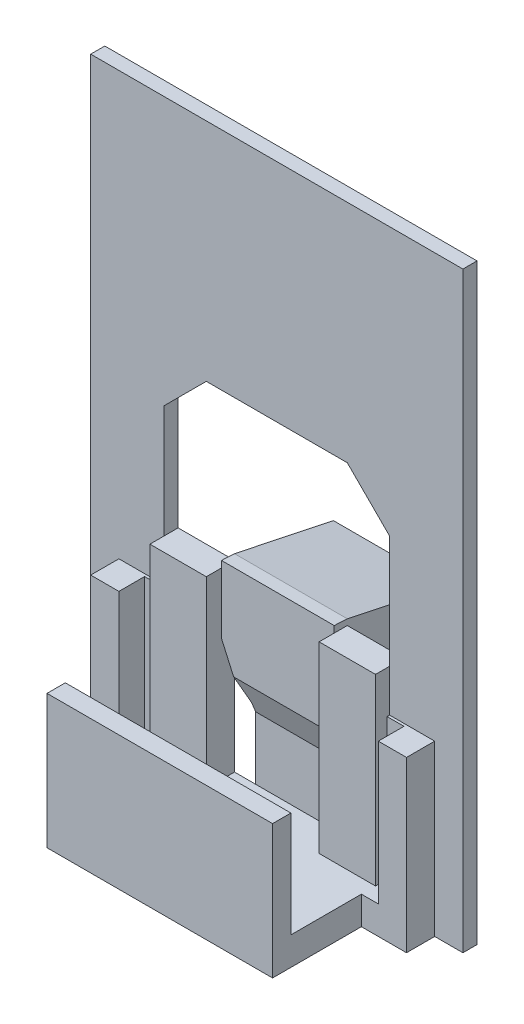
SolidWorks part; units mm, degrees
ref_plane "前视基准面" through (0, 0, 0) normal (0, 0, 1) x (1, 0, 0)
ref_plane "上视基准面" through (0, 0, 0) normal (0, 1, 0) x (1, 0, 0)
ref_plane "右视基准面" through (0, 0, 0) normal (1, 0, 0) x (0, 0, -1)
sketch "草图1" plane through (0, 0, 0) normal (0, 1, 0) x (1, 0, 0)
  line L1 (8, -4.75) -> (-8, -4.75)
  line L2 (8, -4.75) -> (8, 4.75)
  line L3 (8, 4.75) -> (-8, 4.75)
  line L4 (-8, -4.75) -> (-8, 4.75)
  line L5 (8, -4.75) -> (-8, 4.75) construction
  line L6 (8, 4.75) -> (-8, -4.75) construction
  line L7 (8, 4.75) -> (-8, 4.75)
  line L8 (8, 4.75) -> (8, 2.75)
  line L9 (8, 2.75) -> (-8, 2.75)
  line L10 (-8, 4.75) -> (-8, 2.75)
  line L11 (8, -4.75) -> (-8, -4.75)
  line L12 (8, -4.75) -> (8, -3.25)
  line L13 (8, -3.25) -> (-8, -3.25)
  line L14 (-8, -4.75) -> (-8, -3.25)
  point P0 (0, 0)
  dimension "D1" = 6
  dimension "D2" = 9.5
  dimension "D3" = 2
  dimension "D4" = 16
extrude "凸台-拉伸1" add sketch "草图1" along normal blind 2 contours L13 L2 L9 L4 region at (0, 0, 0.25)
extrude "凸台-拉伸2" add sketch "草图1<3>" along normal blind 15 contours L9 L2 L3 L4 | L2 L13 L4 L1 region at (0, 0, 4) region at (0, 0, -3.75)
sketch "草图1<3>" plane through (0, 0, 0) normal (0, 1, 0) x (1, 0, 0) same geometry as "草图1"
sketch "草图2" plane through (0, 0, -4.75) normal (0, 0, -1) x (-1, 0, 0)
  line L0 (0, 12.199) -> (0, -4.867) construction
  line L1 (-8, 15) -> (8, 15) construction
  line L2 (4, 28) -> (-4, 28)
  line L3 (4, 28) -> (4, 2)
  line L4 (4, 2) -> (-4, 2)
  line L5 (-4, 28) -> (-4, 2)
  line L6 (4, 28) -> (-4, 2) construction
  line L7 (4, 2) -> (-4, 28) construction
  line L8 (-8, 2) -> (8, 2) construction
  point P3 (0, 15)
  dimension "D1" = 8
  dimension "D2" = 0
extrude "切除-拉伸1" cut sketch "草图2" against normal up to surface (2 mm away) up to face at (0, 8.5, -2.75)
sketch "草图3" plane through (0, 0, 0) normal (1, 0, 0) x (0, 0, -1)
  line L0 (4.75, 0) -> (8.8316, 0)
  line L3 (4.75, 15.4148) -> (4.75, 0)
  line L4 (4.75, 15.4148) -> (11.7685, 13.9357)
  line L5 (11.7685, 13.9357) -> (8.8316, 0)
  dimension "D1" = 90
extrude "凸台-拉伸3" add sketch "草图3" along normal mid plane 5
sketch "草图4" plane through (8, 0, 0) normal (1, 0, 0) x (0, 0, -1)
  line L0 (2.75, 15) -> (2.75, 2) construction
  line L1 (4.75, 15) -> (2.75, 15)
  line L2 (4.75, 15) -> (4.75, 11.7656)
  line L3 (4.75, 11.7656) -> (2.75, 11.7656)
  line L4 (2.75, 15) -> (2.75, 11.7656)
sketch "草图5" plane through (2.5, 0, 0) normal (1, 0, 0) x (0, 0, -1)
  line L0 (4.75, 6.4511) -> (3.8228, 8.745)
  line L1 (4.75, 15) -> (4.75, 0) construction
  line L2 (3.8228, 8.745) -> (3.8228, 15.4638)
  line L3 (2.7617, 15.5198) -> (10.7506, 15.0981) construction
  line L4 (3.8228, 15.4638) -> (4.75, 15.4148)
  line L5 (4.75, 15.4148) -> (4.75, 6.4511)
extrude "凸台-拉伸4" add sketch "草图5" against normal up to surface (5 mm away) up to face at (-2.5, 6.2701, -6.97)
sketch "草图6" plane through (-2.5, 0, 0) normal (-1, 0, 0) x (0, 0, 1)
  line L0 (-4.75, 6.4511) -> (-10.0949, 5.9946)
  line L7 (-4.75, 2) -> (-4.75, 6.4511)
  line L8 (-4.75, 6.4511) -> (-3.8228, 8.745)
  line L9 (-3.8228, 8.745) -> (-3.8228, 15.4638)
  line L10 (-3.8228, 15.4638) -> (-4.75, 15.4148)
  line L11 (-3.8228, 15.4638) -> (-4.75, 15.4148)
  line L12 (-8.8316, 0) -> (-4.75, 0)
  line L13 (-4.75, 0) -> (-4.75, 2)
  line L15 (-4.75, 6.4511) -> (-3.8228, 8.745)
  line L16 (-3.8228, 8.745) -> (-3.8228, 15.4638)
  line L22 (-4.75, 15.4148) -> (-11.7685, 13.9357)
  line L23 (-4.75, 15.4148) -> (-11.7685, 13.9357)
  line L24 (-11.7685, 13.9357) -> (-8.8316, 0)
  line L25 (-11.7685, 13.9357) -> (-10.0949, 5.9946)
  dimension "D1" = 0
extrude "凸台-拉伸5" add sketch "草图6" along normal up to surface (1.5 mm away) up to face at (-4, 8.5, -3.75)
sketch "草图9" plane through (0, 0, 0) normal (0, -1, 0) x (1, 0, 0)
  line L0 (8, -4.75) -> (11.2, -4.75)
  line L1 (11.2, -4.75) -> (11.2, -1.75)
  line L2 (11.2, -1.75) -> (9.2, -1.75)
  line L4 (8, -3.5704) -> (8, -4.75)
  line L5 (9.2, -1.75) -> (9.2, -3.5704)
  line L6 (9.2, -3.5704) -> (8, -3.5704)
  line L7 (9.2, -1.75) -> (8, -1.75)
  line L8 (8, 4.75) -> (8, -4.75) construction
  line L9 (8, -1.75) -> (8, -3.5704)
  line L10 (0, 0) -> (0, -12.5877) construction
  line L11 (-8, -1.75) -> (-8, -3.5704)
  line L12 (-9.2, -1.75) -> (-8, -1.75)
  line L13 (-9.2, -3.5704) -> (-8, -3.5704)
  line L14 (-9.2, -1.75) -> (-9.2, -3.5704)
  line L15 (-8, -3.5704) -> (-8, -4.75)
  line L16 (-11.2, -1.75) -> (-9.2, -1.75)
  line L17 (-11.2, -4.75) -> (-11.2, -1.75)
  line L18 (-8, -4.75) -> (-11.2, -4.75)
  line M7 (8, -4.75) -> (8, 4.75)
  line M9 (-8, 4.75) -> (-8, -4.75)
  dimension "D1" = 3
  dimension "D2" = 1.2
  dimension "D3" = 2
extrude "凸台-拉伸6" add sketch "草图9" against normal up to surface (2 mm away) contours L5 L7 L6 M7 | L12 L14 L13 M9 region at (8.6, 0, -2.6602) region at (-8.6, 0, -2.6602) up to face at (0, 2, -2.35)
extrude "凸台-拉伸7" add sketch "草图9<3>" against normal blind 12 contours L5 L6 L0 L1 L2 M7 | L18 L13 L14 L16 L17 M9 region at (9.8946, 0, -3.4237) region at (-9.8946, 0, -3.4237)
sketch "草图9<3>" plane through (0, 0, 0) normal (0, -1, 0) x (1, 0, 0) same geometry as "草图9"
sketch "草图11" plane through (0, -1.7821, -8.456) normal (0, -0.2062, -0.9785) x (-1, 0, 0)
  line L0 (2.5, 7.9475) -> (4, 11.2453)
  line L1 (4, 16.063) -> (4, 7.9475) construction
  line L2 (4, 11.2453) -> (4, 7.9475)
  line L4 (4, 7.9475) -> (4, 5.815)
  line L5 (4, 5.815) -> (2.5, 5.815)
  line L6 (2.5, 5.815) -> (2.5, 7.9475)
extrude "切除-拉伸2" cut sketch "草图11" against normal up to surface (5.9605 mm away) up to face at (-1.4, 12.6835, -3.8228)
mirror "镜向1" about plane through (0, 0, 0) normal (1, 0, 0) of "凸台-拉伸5", "切除-拉伸2"
sketch "草图12" plane through (4, 0, 0) normal (1, 0, 0) x (0, 0, -1)
  circle A0 centre (9.1836, 11.7521) radius 1.2818
extrude "切除-拉伸3" cut sketch "草图12" against normal blind 10
sketch "草图13" plane through (8, 0, 0) normal (1, 0, 0) x (0, 0, -1)
  line L0 (-3.25, 9.4845) -> (-4.55, 9.4845)
  line L1 (-3.25, 15) -> (-3.25, 2) construction
  line L2 (-4.55, 9.4845) -> (-4.55, 0)
  line L3 (-4.75, 0) -> (1.75, 0) construction
  line L4 (-4.55, 0) -> (-4.75, 0)
  line L5 (-4.75, 0) -> (-4.75, 15)
  line L6 (-4.75, 15) -> (-3.25, 15)
  line L7 (-4.75, 15) -> (-3.25, 15) construction
  line L8 (-3.25, 15) -> (-3.25, 9.4845)
  dimension "D1" = 1.3
extrude "切除-拉伸4" cut sketch "草图13" against normal through all
sketch "草图14" plane through (0, 12, 0) normal (0, 1, 0) x (1, 0, 0)
  line L0 (8, 4.75) -> (8, 2.75) construction
  line L1 (8, 3.75) -> (13.2, 3.75)
  line L2 (8, 3.75) -> (8, 4.75)
  line L3 (8, 4.75) -> (13.2, 4.75)
  line L4 (13.2, 3.75) -> (13.2, 4.75)
  line L5 (11.2, 4.75) -> (11.2, 1.75) construction
  line L6 (0, 16.3838) -> (0, -10.165) construction
  line L7 (-13.2, 3.75) -> (-13.2, 4.75)
  line L8 (-8, 4.75) -> (-13.2, 4.75)
  line L9 (-8, 3.75) -> (-8, 4.75)
  line L10 (-8, 3.75) -> (-13.2, 3.75)
  dimension "D1" = 2
extrude "凸台-拉伸8" add sketch "草图14" along normal blind 30
extrude "凸台-拉伸9" add sketch "草图14<2>" against normal up to surface (12 mm away) up to face at (0, 0, -2.8803)
sketch "草图14<2>" plane through (0, 12, 0) normal (0, 1, 0) x (1, 0, 0) same geometry as "草图14"
sketch "草图15" plane through (-8, 0, 0) normal (1, 0, 0) x (0, 0, -1)
  line L0 (3.75, 42) -> (3.75, 15) construction
  line L1 (4.75, 42) -> (3.75, 42)
  line L2 (4.75, 42) -> (4.75, 26)
  line L3 (4.75, 26) -> (3.75, 26)
  line L4 (3.75, 42) -> (3.75, 26)
  dimension "D1" = 16
extrude "凸台-拉伸10" add sketch "草图15" along normal up to surface (16 mm away) up to face at (8, 28.5, -4.25)
chamfer "倒角1" distance 3 angle 45 2 edges at (8, 26, -4.25) (-8, 26, -4.25)
